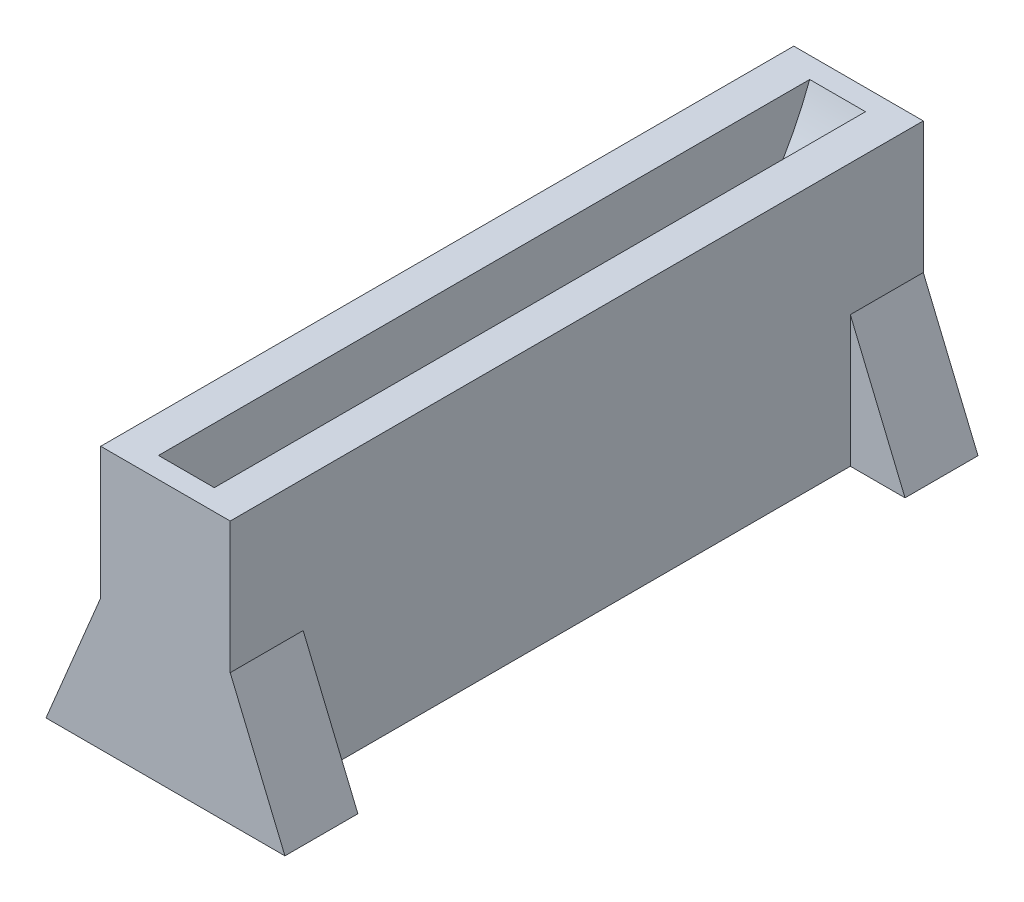
SolidWorks part; units mm, degrees
ref_plane "Front Plane" through (0, 0, 0) normal (0, 0, 1) x (1, 0, 0)
ref_plane "Top Plane" through (0, 0, 0) normal (0, 1, 0) x (1, 0, 0)
ref_plane "Right Plane" through (0, 0, 0) normal (1, 0, 0) x (0, 0, -1)
sketch "Sketch1" plane through (0, 0, 0) normal (0, 1, 0) x (1, 0, 0)
  line L1 (-17.75, 95) -> (17.75, 95)
  line L2 (-17.75, 95) -> (-17.75, -95)
  line L3 (-17.75, -95) -> (17.75, -95)
  line L4 (17.75, 95) -> (17.75, -95)
  line L5 (-17.75, 95) -> (17.75, -95) construction
  line L6 (-17.75, -95) -> (17.75, 95) construction
  point P0 (0, 0)
  dimension "D1" = 35.5
  dimension "D2" = 190
extrude "Boss-Extrude1" add sketch "Sketch1" along normal blind 72
sketch "Sketch2" plane through (0, 0, 0) normal (1, 0, 0) x (0, 0, -1)
  line L0 (0, 0) -> (0, 190.5) construction
  line L1 (0, 95.25) -> (0, 105.25) construction
  circle A1 centre (0, 105.25) radius 95.25
  dimension "D3" = 190.5
  dimension "D1" = 190.5
  dimension "D2" = 10
extrude "Cut-Extrude15" cut sketch "Sketch2" against normal blind 7.65 and the other way blind 7.65
sketch "Sketch6" plane through (0, 0, 0) normal (0, 0, 1) x (1, 0, 0)
  line L0 (-17.75, 0) -> (-32.75, 0)
  line L1 (-32.75, 0) -> (-17.75, 36)
  line L2 (-17.75, 72) -> (-17.75, 0) construction
  line L3 (-17.75, 36) -> (-17.75, 0)
  line L4 (17.75, 0) -> (32.75, 0)
  line L5 (32.75, 0) -> (17.75, 36)
  line L6 (17.75, 72) -> (17.75, 0) construction
  line L7 (17.75, 36) -> (17.75, 0)
  dimension "D1" = 15
  dimension "D2" = 15
extrude "Boss-Extrude5" add sketch "Sketch6" along normal blind 95 and the other way blind 95
sketch "Sketch7" plane through (0, 0, 0) normal (0, 1, 0) x (1, 0, 0)
  line L0 (-59.12, 75) -> (-59.12, -75)
  line L1 (-59.12, -75) -> (-17.75, -75)
  line L2 (-17.75, -75) -> (-17.75, 75)
  line L3 (-17.75, 75) -> (-59.12, 75)
  line L4 (-32.75, -95) -> (32.75, -95) construction
  line L5 (32.75, 95) -> (-32.75, 95) construction
  line L6 (-17.75, 95) -> (-17.75, -95) construction
  dimension "D1" = 20
  dimension "D2" = 20
  dimension "D3" = 0
extrude "Cut-Extrude16" cut sketch "Sketch7" along normal blind 45
sketch "Sketch8" plane through (0, 0, 0) normal (0, 1, 0) x (1, 0, 0)
  line L0 (17.75, 75) -> (17.75, -75)
  line L1 (17.75, -75) -> (90.3347, -75)
  line L2 (90.3347, -75) -> (90.3347, 75)
  line L3 (90.3347, 75) -> (17.75, 75)
  line L4 (32.75, -95) -> (17.75, -95) construction
  line L5 (32.75, 95) -> (17.75, 95) construction
  line L6 (17.75, 95) -> (17.75, -95) construction
  dimension "D1" = 20
  dimension "D2" = 20
  dimension "D3" = 0
extrude "Cut-Extrude17" cut sketch "Sketch8" along normal blind 45
